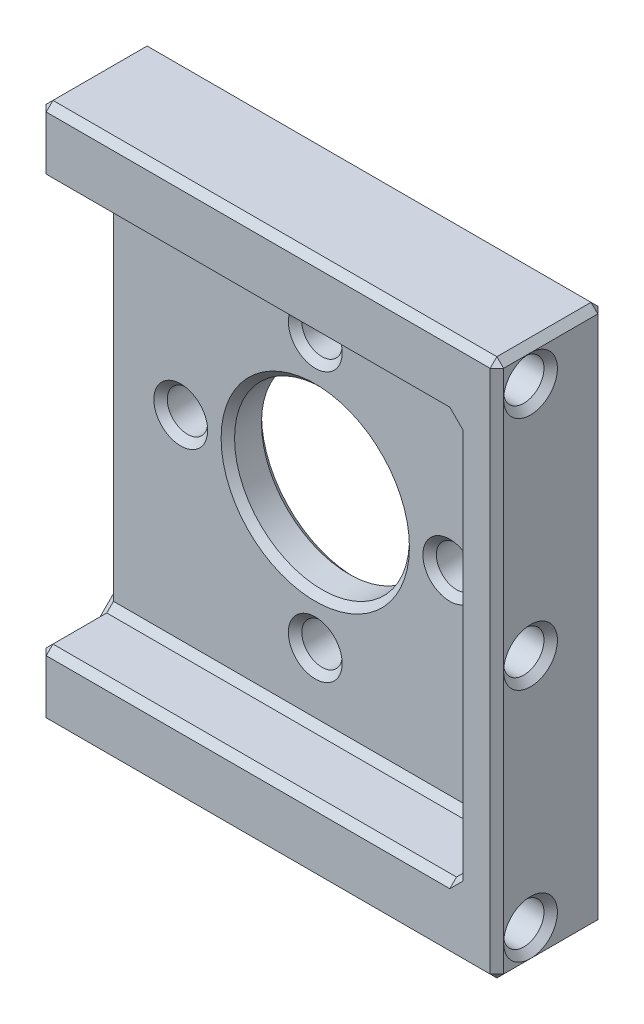
SolidWorks part; units mm, degrees
ref_plane "Plan de face" through (0, 0, 0) normal (0, 0, 1) x (1, 0, 0)
ref_plane "Plan de dessus" through (0, 0, 0) normal (0, 1, 0) x (1, 0, 0)
ref_plane "Plan de droite" through (0, 0, 0) normal (1, 0, 0) x (0, 0, -1)
sketch "Esquisse1" plane through (0, 0, 0) normal (0, 0, 1) x (1, 0, 0)
  line L1 (0, 0) -> (34, 0)
  line L2 (0, 0) -> (0, 40)
  line L3 (0, 40) -> (34, 40)
  line L4 (34, 0) -> (34, 40)
  dimension "D1" = 34
  dimension "D2" = 40
extrude "Boss.-Extru.1" add sketch "Esquisse1" along normal blind 3
sketch "Esquisse2" plane through (0, 0, 3) normal (0, 0, 1) x (1, 0, 0)
  line L0 (31, 40) -> (0, 0) construction
  line L1 (34, 40) -> (0, 40) construction
  line L2 (34, 0) -> (34, 40) construction
  circle A0 centre (15.5, 20) radius 6.5
  point P6 (34, 40)
  point P7 (28.1324, 40)
  dimension "D1" = 13
  dimension "D2" = 3
extrude "Enlèv. mat.-Extru.1" cut sketch "Esquisse2" against normal blind 4
sketch "Esquisse5" plane through (0, 0, 3) normal (0, 0, 1) x (1, 0, 0)
  line L0 (15.5, 30) -> (15.5, 20) construction
  line L1 (15.5, 20) -> (25.5, 20) construction
  line L2 (5.5, 20) -> (15.5, 20) construction
  line L3 (15.5, 20) -> (15.5, 10) construction
  circle A0 centre (15.5, 30) radius 1.5
  circle A1 centre (5.5, 20) radius 1.5
  circle A2 centre (15.5, 10) radius 1.5
  circle A3 centre (25.5, 20) radius 1.5
  dimension "D1" = 3
  dimension "D2" = 3
  dimension "D3" = 3
  dimension "D4" = 3
  dimension "D5" = 10
  dimension "D6" = 90
  dimension "D7" = 90
  dimension "D8" = 90
extrude "Enlèv. mat.-Extru.3" cut sketch "Esquisse5" against normal blind 5
sketch "Esquisse9" plane through (0, 0, 3) normal (0, 0, 1) x (1, 0, 0)
  line L0 (34, 0) -> (34, 40) construction
  line L1 (0, 40) -> (34, 40)
  line L2 (0, 40) -> (0, 35)
  line L3 (0, 35) -> (34, 35)
  line L4 (34, 40) -> (34, 35)
  line L5 (15.5, 20) -> (0, 20) construction
  line L6 (0, 40) -> (0, 0) construction
  line L7 (0, 5) -> (34, 5)
  line L8 (34, 0) -> (34, 5)
  line L9 (0, 0) -> (34, 0)
  line L10 (0, 0) -> (0, 5)
  dimension "D1" = 5
extrude "Boss.-Extru.5" add sketch "Esquisse9" along normal blind 5
sketch "Esquisse10" plane through (34, 0, 0) normal (1, 0, 0) x (0, 0, -1)
  line L0 (-8, 40) -> (-3, 35) construction
  line L1 (-3, 20) -> (0, 20) construction
  line L2 (-3, 5) -> (-3, 35) construction
  line L3 (0, 0) -> (0, 40) construction
  circle A0 centre (-5.5, 37.5) radius 1.5
  circle A1 centre (-5.5, 2.5) radius 1.5
  dimension "D1" = 3
extrude "Enlèv. mat.-Extru.6" cut sketch "Esquisse10" against normal through all
sketch "Esquisse11" plane through (0, 0, 3) normal (0, 0, 1) x (1, 0, 0)
  line L0 (34, 5) -> (0, 5) construction
  line L1 (34, 35) -> (31, 35)
  line L2 (34, 35) -> (34, 5)
  line L3 (34, 5) -> (31, 5)
  line L4 (31, 35) -> (31, 5)
  dimension "D1" = 3
extrude "Boss.-Extru.6" add sketch "Esquisse11" along normal blind 5
sketch "Esquisse12" plane through (34, 0, 0) normal (1, 0, 0) x (0, 0, -1)
  line L0 (-5.5, 37.5) -> (-5.5, 2.5) construction
  circle A0 centre (-5.5, 20) radius 1.5
  dimension "D1" = 3
extrude "Enlèv. mat.-Extru.7" cut sketch "Esquisse12" against normal blind 5
chamfer "Chanfrein1" distance 0.5 angle 45 40 edges at (9, 20, 0) (22, 20, 3) (14, 30, 0) (4, 20, 0) (14, 10, 0) (24, 20, 0) (17, 30, 3) (7, 20, 3) (17, 10, 3) (27, 20, 3) (0, 37.5, 4) (34, 37.5, 4) (0, 2.5, 7) (34, 2.5, 7) (0, 0, 4) (34, 0, 4) (34, 40, 4) (17, 40, 0) (34, 20, 0) (17, 0, 0) (0, 20, 0) (0, 40, 4) (0, 20, 3) (0, 35, 5.5) (17, 40, 8) (34, 20, 8) (0, 37.5, 8) (15.5, 35, 8) (15.5, 35, 3) (0, 5, 5.5) (17, 0, 8) (0, 2.5, 8) (15.5, 5, 8) (15.5, 5, 3) (31, 35, 5.5) (31, 20, 8) (31, 5, 5.5) (31, 20, 3) (31, 20, 4) (34, 20, 4)
